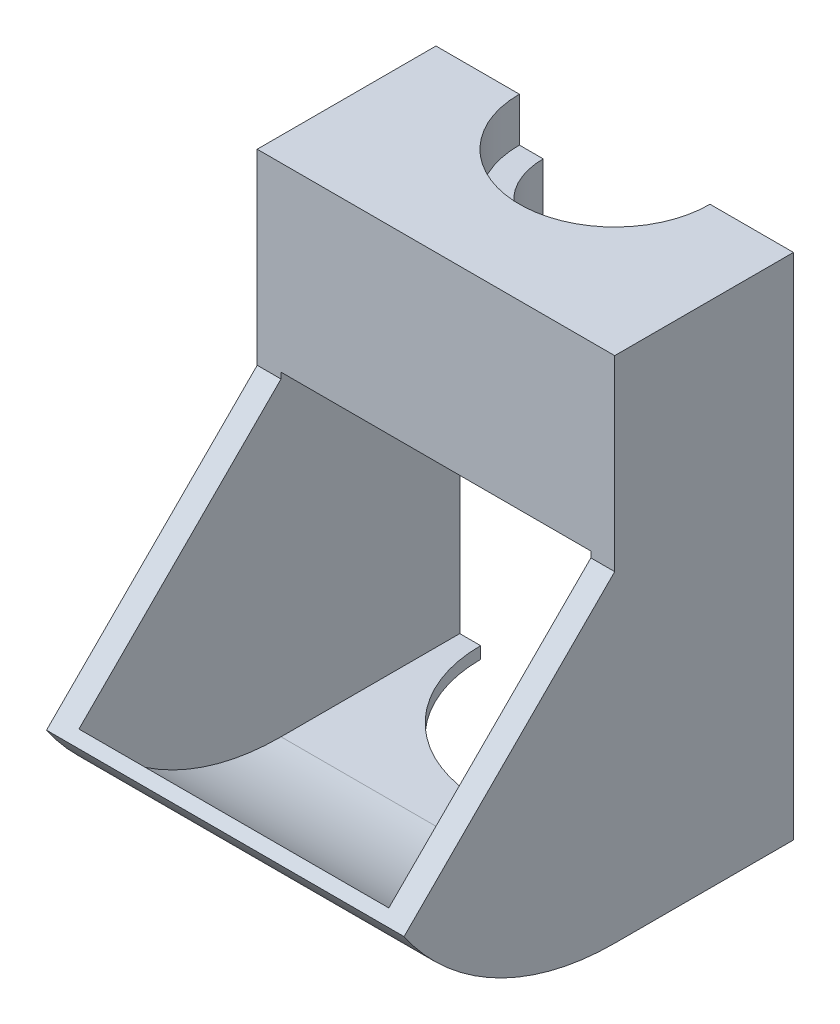
SolidWorks part; units mm, degrees
ref_plane "Front Plane" through (0, 0, 0) normal (0, 0, 1) x (1, 0, 0)
ref_plane "Top Plane" through (0, 0, 0) normal (0, 1, 0) x (1, 0, 0)
ref_plane "Right Plane" through (0, 0, 0) normal (1, 0, 0) x (0, 0, -1)
sketch "Sketch2" plane through (0, 0, 0) normal (0, 0, 1) x (1, 0, 0)
  line L1 (-15, 0) -> (15, 0)
  line L2 (-15, 0) -> (-15, 42.7)
  line L3 (-15, 42.7) -> (15, 42.7)
  line L4 (15, 0) -> (15, 42.7)
  line L5 (0, 42.7) -> (0, 0) construction
  line L6 (-15, 21.35) -> (15, 21.35) construction
  point P120 (0, 21.35)
  dimension "D1" = 30
  dimension "D2" = 42.7
extrude "Boss-Extrude1" add sketch "Sketch2" along normal blind 15
sketch "Sketch3" plane through (0, 0, 0) normal (1, 0, 0) x (0, 0, -1)
  line L0 (-15, 0) -> (-15, 42.7)
  line L1 (-15, 0) -> (-15, 42.7)
  line L2 (-15, 27) -> (-32.6777, 9.3223)
  line L3 (-15, 42.7) -> (-15, 0) construction
  line L4 (-15, 0) -> (0, 0) construction
  arc A0 (-32.6777, 9.3223) -> (-15, 0) centre (-15, 21.422) ccw
  dimension "D1" = 25
  dimension "D2" = 45
  dimension "D3" = 27
extrude "Boss-Extrude2" add sketch "Sketch3" along normal mid plane 30 contours L2 A0 L1 region at (0, 11.0865, 21.3107)
sketch "Sketch4" plane through (0, 0, 0) normal (0, 0, -1) x (-1, 0, 0)
  line L0 (0, 51.4794) -> (0, -30.0904) construction
  line L1 (0, 42.7) -> (8, 42.7)
  line L2 (8, 42.7) -> (8, 39)
  line L3 (8, 39) -> (6, 39)
  line L4 (6, 39) -> (6, 33)
  line L5 (6, 33) -> (8, 33)
  line L6 (8, 33) -> (8, 27.5)
  line L7 (-15, 42.7) -> (15, 42.7) construction
  line L8 (0, 0) -> (0, 42.7)
  line L10 (8, 27.5) -> (11.25, 27.5)
  line L11 (11.25, 27.5) -> (11.25, 0)
  line L12 (15, 0) -> (-15, 0) construction
  line L13 (11.25, 0) -> (0, 0)
  dimension "D1" = 16
  dimension "D2" = 12
  dimension "D3" = 3.7
  dimension "D4" = 6
  dimension "D5" = 5.5
  dimension "D6" = 22.5
revolve "Cut-Revolve1" cut sketch "Sketch4" angle 360 about L0
sketch "Sketch5" plane through (0, 0, 0) normal (1, 0, 0) x (0, 0, -1)
  line L0 (-31.9576, 10.0424) -> (-15.7071, 26.2929)
  line L1 (-15, 27) -> (-32.6777, 9.3223) construction
  line L2 (-15.7071, 26.2929) -> (-16.9142, 27.5)
  line L3 (-16.9142, 27.5) -> (-11.25, 27.5)
  line L4 (-11.25, 27.5) -> (0, 27.5) construction
  line L5 (-11.25, 27.5) -> (0, 27.5)
  line L6 (0, 27.5) -> (0, 1)
  line L7 (-15, 1) -> (0, 1)
  line L8 (-11.25, 0) -> (-15, 0)
  line L9 (-11.25, 0) -> (-15, 0) construction
  arc A0 (-15, 1) -> (-31.9576, 10.0424) centre (-15, 21.422) cw
  arc A1 (-32.6777, 9.3223) -> (-15, 0) centre (-15, 21.422) ccw
  arc A2 (-32.6777, 9.3223) -> (-15, 0) centre (-15, 21.422) ccw construction
  dimension "D1" = 1
  dimension "D2" = 1
extrude "Cut-Extrude1" cut sketch "Sketch5" against normal mid plane 26
